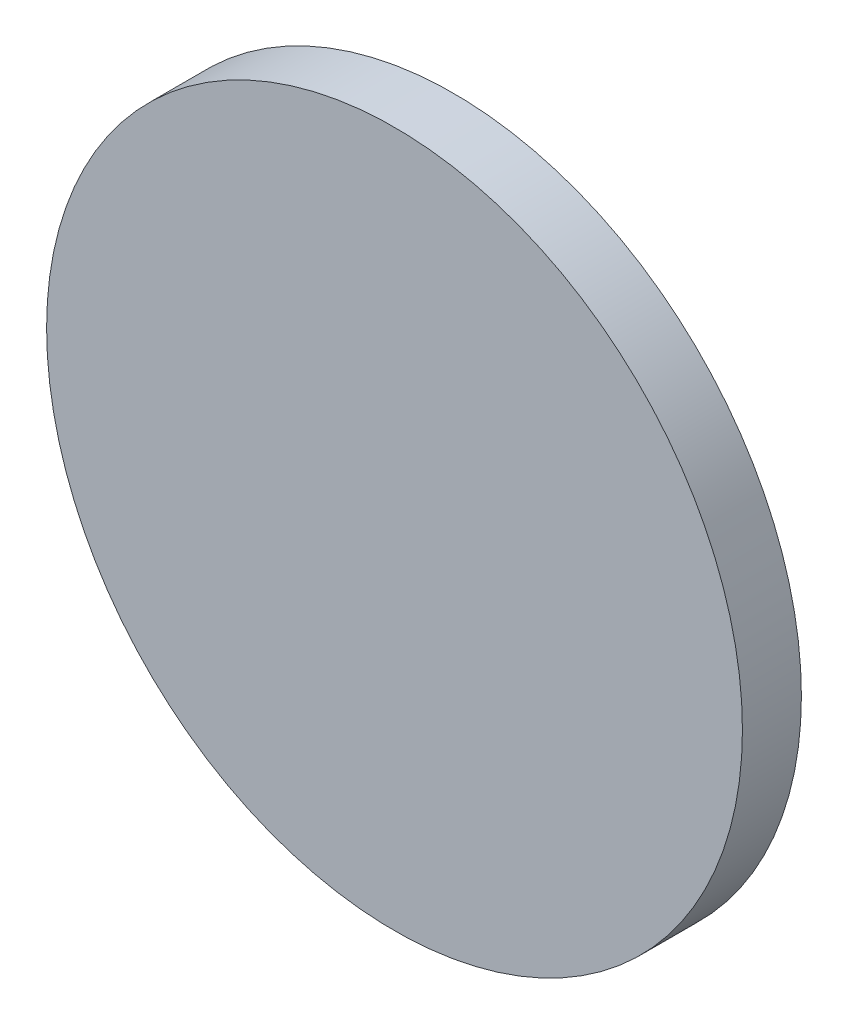
SolidWorks part; units mm, degrees
ref_plane "Front" through (0, 0, 0) normal (0, 0, 1) x (1, 0, 0)
ref_plane "Top" through (0, 0, 0) normal (0, 1, 0) x (1, 0, 0)
ref_plane "Right" through (0, 0, 0) normal (1, 0, 0) x (0, 0, -1)
other "Configuration Table"
sketch "Sketch1" plane through (0, 0, 0) normal (0, 0, 1) x (1, 0, 0)
  circle A0 centre (0, 0) radius 58.9984
extrude "Boss-Extrude1" add sketch "Sketch1" along normal blind 10
